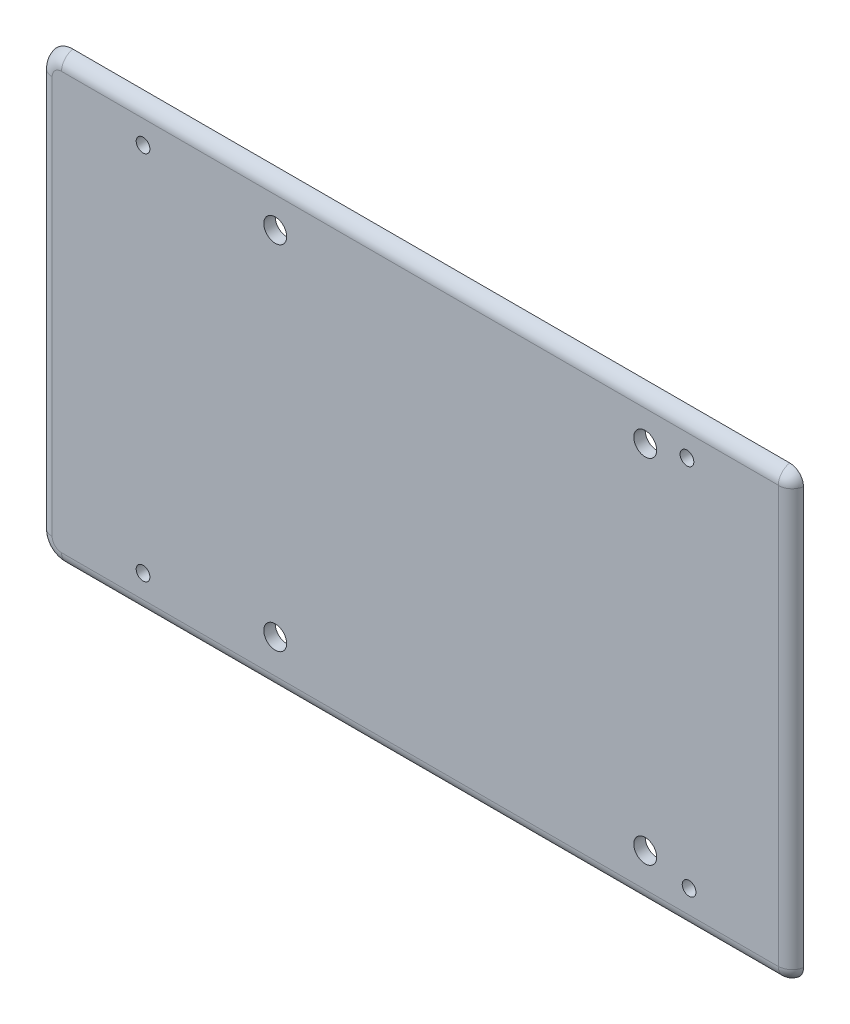
SolidWorks part; units mm, degrees
ref_plane "Alzado" through (0, 0, 0) normal (0, 0, 1) x (1, 0, 0)
ref_plane "Planta" through (0, 0, 0) normal (0, 1, 0) x (1, 0, 0)
ref_plane "Vista lateral" through (0, 0, 0) normal (1, 0, 0) x (0, 0, -1)
sketch "Croquis1" plane through (0, 0, 0) normal (0, 0, 1) x (1, 0, 0)
  line L4 (-71.8143, 92) -> (-71.8143, 5)
  line L5 (-66.8143, 0) -> (89.8154, 0)
  line L6 (92.8154, 3) -> (92.8154, 94)
  line L7 (89.8154, 97) -> (-66.8143, 97)
  line L8 (-71.8143, 92) -> (-71.8143, 5)
  line L9 (-66.8143, 0) -> (89.8154, 0)
  line L10 (92.8154, 3) -> (92.8154, 94)
  line L11 (89.8154, 97) -> (-66.8143, 97)
  circle A0 centre (69.8502, 89.2089) radius 1.5 construction
  circle A1 centre (-49, 89) radius 1.5 construction
  circle A2 centre (-49, 8) radius 1.5 construction
  circle A3 centre (70.3154, 8) radius 1.5 construction
  arc A4 (-71.8143, 5) -> (-66.8143, 0) centre (-66.8143, 5) ccw
  arc A5 (89.8154, 0) -> (92.8154, 3) centre (89.8154, 3) ccw
  arc A6 (92.8154, 94) -> (89.8154, 97) centre (89.8154, 94) ccw
  arc A7 (-66.8143, 97) -> (-71.8143, 92) centre (-66.8143, 92) ccw
  arc A8 (-71.8143, 5) -> (-66.8143, 0) centre (-66.8143, 5) ccw
  arc A9 (89.8154, 0) -> (92.8154, 3) centre (89.8154, 3) ccw
  arc A10 (92.8154, 94) -> (89.8154, 97) centre (89.8154, 94) ccw
  arc A11 (-66.8143, 97) -> (-71.8143, 92) centre (-66.8143, 92) ccw
  circle A12 centre (69.8502, 89.2089) radius 1.5
  circle A13 centre (-49, 89) radius 1.5
  circle A14 centre (-49, 8) radius 1.5
  circle A15 centre (70.3154, 8) radius 1.5
  dimension "D1" = 0
extrude "Saliente-Extruir2" add sketch "Croquis1" along normal blind 2.5
sketch "Croquis2" plane through (0, 0, 2.5) normal (0, 0, 1) x (1, 0, 0)
  circle A0 centre (60.7315, 10.3502) radius 2.5
  circle A1 centre (60.7315, 87.3502) radius 2.5
  circle A2 centre (-20.1176, 10.3502) radius 2.5
  circle A3 centre (-20.1176, 87.3502) radius 2.5
extrude "Cortar-Extruir1" cut sketch "Croquis2" against normal blind 2.5
fillet "Redondeo1" radius 3 8 edges at (91.9367, 0.8787, 2.5) (11.5006, 0, 2.5) (-70.3498, 1.4645, 2.5) (-71.8143, 48.5, 2.5) (-70.3498, 95.5355, 2.5) (11.5006, 97, 2.5) (91.9367, 96.1213, 2.5) (92.8154, 48.5, 2.5)
